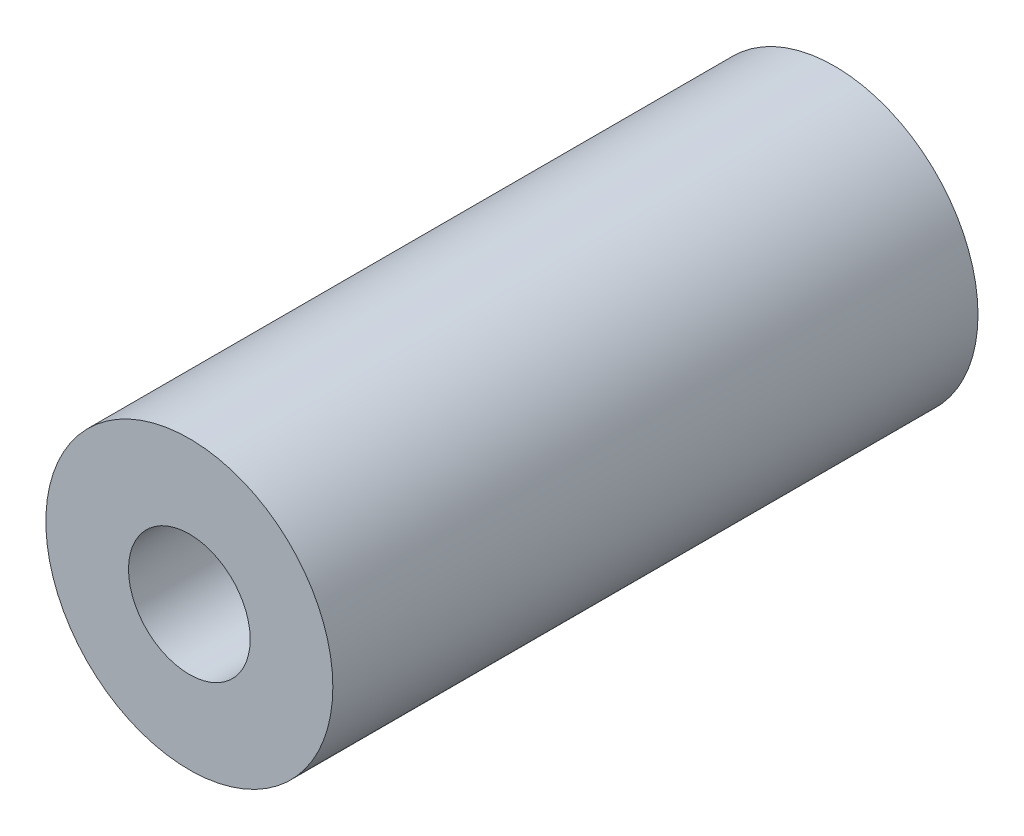
SolidWorks part; units mm, degrees
material "6061-T6 (SS)"
ref_plane "Front Plane" through (0, 0, 0) normal (0, 0, 1) x (1, 0, 0)
ref_plane "Top Plane" through (0, 0, 0) normal (0, 1, 0) x (1, 0, 0)
ref_plane "Right Plane" through (0, 0, 0) normal (1, 0, 0) x (0, 0, -1)
sketch "Sketch1" plane through (0, 0, 0) normal (0, 0, 1) x (1, 0, 0)
  circle A0 centre (0, 0) radius 4.7625
  dimension "D1" = 9.525
extrude "Boss-Extrude1" add sketch "Sketch1" along normal mid plane 21.4122
hole_wizard "#10-32 Tapped Hole2" positions "3DSketch1" profile "Sketch4" tap size "#10-32" standard "ANSI Inch"
sketch3d "3DSketch1"
  line L0 (0, 0, 10.7061) -> (0, 0, -10.7061) construction
  point P0 (0, 0, 10.7061)
  point P4 (0, 0, -10.7061)
sketch "Sketch4" plane through (0, 0, 10.7061) normal (1, 0, 0) x (0, -1, 0)
  line L0 (0, 0) -> (0, 16.2908)
  line L1 (0, 16.2908) -> (2.0193, 15.0774)
  line L2 (2.0193, 15.0774) -> (2.0193, 0)
  line L5 (2.0193, 0) -> (0, 0)
  line L10 (0, 16.2908) -> (-2.0193, 15.0774) construction
  line L11 (0, -6.35) -> (0, 107.95) construction
  dimension "Tap Drill Dia." = 4.0386
  dimension "Tap Drill Depth" = 15.0774
  dimension "Drill Angle" = 118
cosmetic thread "Hole Thread2" parameters "D1"=12.7, "D2"=4.826
cosmetic thread "Hole Thread3" parameters "D1"=12.7, "D2"=4.826
